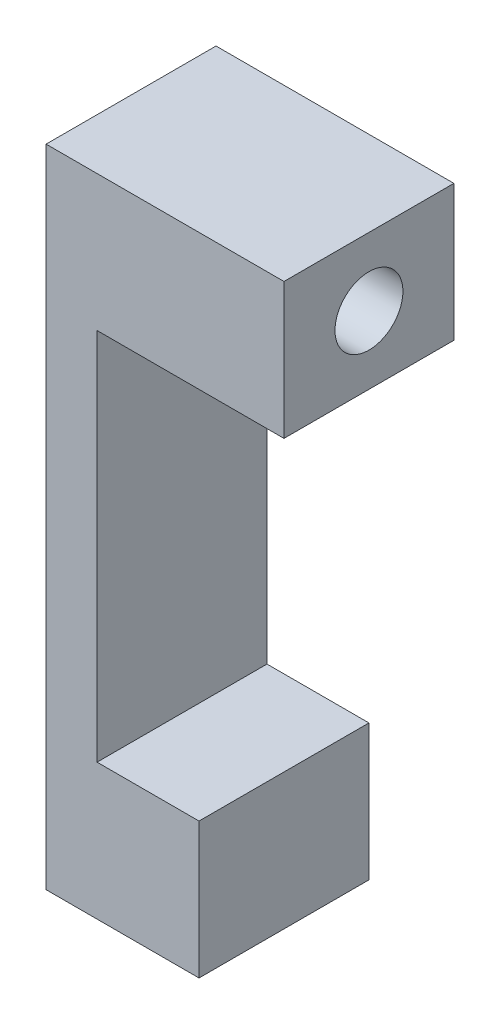
SolidWorks part; units mm, degrees
material "1023 Carbon Steel Sheet (SS)"
ref_plane "Front Plane" through (0, 0, 0) normal (0, 0, 1) x (1, 0, 0)
ref_plane "Top Plane" through (0, 0, 0) normal (0, 1, 0) x (1, 0, 0)
ref_plane "Right Plane" through (0, 0, 0) normal (1, 0, 0) x (0, 0, -1)
sketch "Sketch1" plane through (0, 0, 0) normal (1, 0, 0) x (0, 0, -1)
  line L0 (-25, 55) -> (25, 55)
  line L1 (-25, -95) -> (25, -95)
  line L2 (-25, -95) -> (-25, 95)
  line L3 (-25, 95) -> (25, 95)
  line L4 (25, -95) -> (25, 95)
  line L5 (-25, -95) -> (25, 95) construction
  line L6 (-25, 95) -> (25, -95) construction
  line L7 (-25, -55) -> (25, -55)
  line L8 (-25, 95) -> (25, 55) construction
  line L9 (-25, 55) -> (25, 95) construction
  line L10 (-25, -55) -> (25, -95) construction
  line L11 (-25, -95) -> (25, -55) construction
  line L12 (0, 75) -> (0, -75) construction
  circle A0 centre (0, 75) radius 10
  point P0 (0, 0)
  dimension "D5" = 20
  dimension "D1" = 50
  dimension "D2" = 40
  dimension "D3" = 40
  dimension "D4" = 150
extrude "Boss-Extrude1" add sketch "Sketch1" along normal blind 55 contours L0 L4 L3 L2 region at (0, 75, 24.3597)
extrude "Boss-Extrude2" add sketch "Sketch1<3>" against normal blind 15 contours L0 L4 L3 L2 | L1 L4 L0 L2 | L7 L2 L1 L4 region at (0, 75, 24.3597) region at (0, 0, 0) region at (0, -75, 0)
sketch "Sketch1<3>" plane through (0, 0, 0) normal (1, 0, 0) x (0, 0, -1) same geometry as "Sketch1"
extrude "Boss-Extrude3" add sketch "Sketch1<4>" along normal blind 30 contours L7 L2 L1 L4 region at (0, -75, 0)
sketch "Sketch1<4>" plane through (0, 0, 0) normal (1, 0, 0) x (0, 0, -1) same geometry as "Sketch1"
equation "\"D1@Boss-Extrude1\"= 40 - \"CableGuideDepth\" + 30"
equation "\"CableGuideDepth\"= 15"
